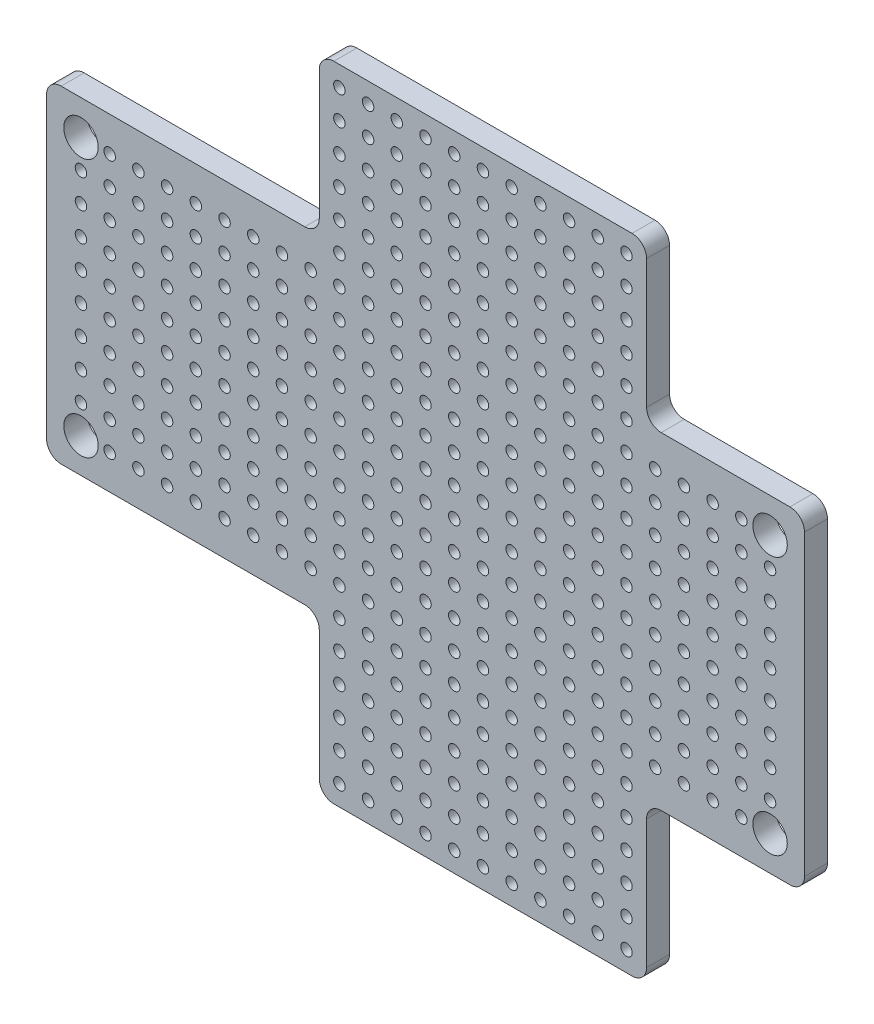
SolidWorks part; units mm, degrees
ref_plane "Front Plane" through (0, 0, 0) normal (0, 0, 1) x (1, 0, 0)
ref_plane "Top Plane" through (0, 0, 0) normal (0, 1, 0) x (1, 0, 0)
ref_plane "Right Plane" through (0, 0, 0) normal (1, 0, 0) x (0, 0, -1)
sketch "Sketch1" plane through (0, 0, 0) normal (0, 0, 1) x (1, 0, 0)
  line L0 (0, 14.25) -> (76, 14.25) construction
  line L1 (0, 0) -> (23.75, 0)
  line L2 (0, 0) -> (0, 28.5)
  line L3 (0, 28.5) -> (23.75, 28.5)
  line L4 (66, 0) -> (66, 28.5)
  line L5 (38, -42.734) -> (38, 127.234) construction
  line L6 (0, 25.5) -> (76, 25.5) construction
  line L7 (76, 3) -> (0, 3) construction
  line L8 (63, 0) -> (63, 28.5) construction
  line L9 (3, 0) -> (3, 28.5) construction
  line L12 (23.75, 28.5) -> (23.75, 42.25)
  line L13 (23.75, 42.25) -> (52.25, 42.25)
  line L14 (52.25, 42.25) -> (52.25, 28.5)
  line L15 (52.25, -13.75) -> (52.25, 0)
  line L16 (23.75, -13.75) -> (52.25, -13.75)
  line L17 (23.75, 0) -> (23.75, -13.75)
  line L18 (52.25, 28.5) -> (66, 28.5)
  line L19 (52.25, 0) -> (66, 0)
  line L20 (25.5, 25.5) -> (25.5, 28) construction
  circle A0 centre (3, 25.5) radius 1.5
  circle A1 centre (63, 25.5) radius 1.5
  circle A2 centre (3, 3) radius 1.5
  circle A3 centre (63, 3) radius 1.5
  circle A4 centre (55.5, 5.5) radius 0.5
  circle A5 centre (5.5, 3) radius 0.5
  circle A6 centre (8, 3) radius 0.5
  circle A7 centre (10.5, 3) radius 0.5
  circle A8 centre (13, 3) radius 0.5
  circle A9 centre (15.5, 3) radius 0.5
  circle A10 centre (18, 3) radius 0.5
  circle A11 centre (20.5, 3) radius 0.5
  circle A12 centre (23, 3) radius 0.5
  circle A13 centre (25.5, 3) radius 0.5
  circle A14 centre (28, 3) radius 0.5
  circle A15 centre (30.5, 3) radius 0.5
  circle A16 centre (33, 3) radius 0.5
  circle A17 centre (35.5, 3) radius 0.5
  circle A18 centre (38, 3) radius 0.5
  circle A19 centre (40.5, 3) radius 0.5
  circle A20 centre (43, 3) radius 0.5
  circle A21 centre (45.5, 3) radius 0.5
  circle A22 centre (48, 3) radius 0.5
  circle A23 centre (50.5, 3) radius 0.5
  circle A24 centre (55.5, 10.5) radius 0.5
  circle A25 centre (55.5, 8) radius 0.5
  circle A26 centre (55.5, 15.5) radius 0.5
  circle A27 centre (55.5, 18) radius 0.5
  circle A28 centre (55.5, 20.5) radius 0.5
  circle A29 centre (55.5, 23) radius 0.5
  circle A30 centre (53, 3) radius 0.5
  circle A31 centre (53, 25.5) radius 0.5
  circle A32 centre (58, 5.5) radius 0.5
  circle A33 centre (5.5, 5.5) radius 0.5
  circle A34 centre (8, 5.5) radius 0.5
  circle A35 centre (10.5, 5.5) radius 0.5
  circle A36 centre (13, 5.5) radius 0.5
  circle A37 centre (15.5, 5.5) radius 0.5
  circle A38 centre (18, 5.5) radius 0.5
  circle A39 centre (20.5, 5.5) radius 0.5
  circle A40 centre (23, 5.5) radius 0.5
  circle A41 centre (25.5, 5.5) radius 0.5
  circle A42 centre (28, 5.5) radius 0.5
  circle A43 centre (30.5, 5.5) radius 0.5
  circle A44 centre (33, 5.5) radius 0.5
  circle A45 centre (35.5, 5.5) radius 0.5
  circle A46 centre (38, 5.5) radius 0.5
  circle A47 centre (40.5, 5.5) radius 0.5
  circle A48 centre (43, 5.5) radius 0.5
  circle A49 centre (45.5, 5.5) radius 0.5
  circle A50 centre (48, 5.5) radius 0.5
  circle A51 centre (50.5, 5.5) radius 0.5
  circle A52 centre (53, 5.5) radius 0.5
  circle A53 centre (58, 10.5) radius 0.5
  circle A54 centre (58, 8) radius 0.5
  circle A55 centre (58, 15.5) radius 0.5
  circle A56 centre (58, 18) radius 0.5
  circle A57 centre (58, 20.5) radius 0.5
  circle A58 centre (58, 23) radius 0.5
  circle A59 centre (55.5, 3) radius 0.5
  circle A60 centre (55.5, 25.5) radius 0.5
  circle A61 centre (5.5, 8) radius 0.5
  circle A62 centre (8, 8) radius 0.5
  circle A63 centre (10.5, 8) radius 0.5
  circle A64 centre (13, 8) radius 0.5
  circle A65 centre (15.5, 8) radius 0.5
  circle A66 centre (18, 8) radius 0.5
  circle A67 centre (20.5, 8) radius 0.5
  circle A68 centre (23, 8) radius 0.5
  circle A69 centre (25.5, 8) radius 0.5
  circle A70 centre (28, 8) radius 0.5
  circle A71 centre (30.5, 8) radius 0.5
  circle A72 centre (33, 8) radius 0.5
  circle A73 centre (35.5, 8) radius 0.5
  circle A74 centre (38, 8) radius 0.5
  circle A75 centre (40.5, 8) radius 0.5
  circle A76 centre (43, 8) radius 0.5
  circle A77 centre (45.5, 8) radius 0.5
  circle A78 centre (48, 8) radius 0.5
  circle A79 centre (50.5, 8) radius 0.5
  circle A80 centre (53, 8) radius 0.5
  circle A81 centre (60.5, 5.5) radius 0.5
  circle A82 centre (60.5, 10.5) radius 0.5
  circle A83 centre (60.5, 8) radius 0.5
  circle A84 centre (60.5, 15.5) radius 0.5
  circle A85 centre (60.5, 18) radius 0.5
  circle A86 centre (60.5, 20.5) radius 0.5
  circle A87 centre (60.5, 23) radius 0.5
  circle A88 centre (58, 3) radius 0.5
  circle A89 centre (5.5, 10.5) radius 0.5
  circle A90 centre (8, 10.5) radius 0.5
  circle A91 centre (10.5, 10.5) radius 0.5
  circle A92 centre (13, 10.5) radius 0.5
  circle A93 centre (15.5, 10.5) radius 0.5
  circle A94 centre (18, 10.5) radius 0.5
  circle A95 centre (20.5, 10.5) radius 0.5
  circle A96 centre (23, 10.5) radius 0.5
  circle A97 centre (25.5, 10.5) radius 0.5
  circle A98 centre (28, 10.5) radius 0.5
  circle A99 centre (30.5, 10.5) radius 0.5
  circle A100 centre (33, 10.5) radius 0.5
  circle A101 centre (35.5, 10.5) radius 0.5
  circle A102 centre (38, 10.5) radius 0.5
  circle A103 centre (40.5, 10.5) radius 0.5
  circle A104 centre (43, 10.5) radius 0.5
  circle A105 centre (45.5, 10.5) radius 0.5
  circle A106 centre (48, 10.5) radius 0.5
  circle A107 centre (50.5, 10.5) radius 0.5
  circle A108 centre (53, 10.5) radius 0.5
  circle A109 centre (58, 25.5) radius 0.5
  circle A110 centre (63, 5.5) radius 0.5
  circle A111 centre (63, 10.5) radius 0.5
  circle A112 centre (63, 8) radius 0.5
  circle A113 centre (63, 15.5) radius 0.5
  circle A114 centre (63, 18) radius 0.5
  circle A115 centre (63, 20.5) radius 0.5
  circle A116 centre (63, 23) radius 0.5
  circle A117 centre (5.5, 13) radius 0.5
  circle A118 centre (8, 13) radius 0.5
  circle A119 centre (10.5, 13) radius 0.5
  circle A120 centre (13, 13) radius 0.5
  circle A121 centre (15.5, 13) radius 0.5
  circle A122 centre (18, 13) radius 0.5
  circle A123 centre (20.5, 13) radius 0.5
  circle A124 centre (23, 13) radius 0.5
  circle A125 centre (25.5, 13) radius 0.5
  circle A126 centre (28, 13) radius 0.5
  circle A127 centre (30.5, 13) radius 0.5
  circle A128 centre (33, 13) radius 0.5
  circle A129 centre (35.5, 13) radius 0.5
  circle A130 centre (38, 13) radius 0.5
  circle A131 centre (40.5, 13) radius 0.5
  circle A132 centre (43, 13) radius 0.5
  circle A133 centre (45.5, 13) radius 0.5
  circle A134 centre (48, 13) radius 0.5
  circle A135 centre (50.5, 13) radius 0.5
  circle A136 centre (53, 13) radius 0.5
  circle A137 centre (60.5, 3) radius 0.5
  circle A138 centre (60.5, 25.5) radius 0.5
  circle A139 centre (55.5, 13) radius 0.5
  circle A140 centre (58, 13) radius 0.5
  circle A141 centre (60.5, 13) radius 0.5
  circle A142 centre (63, 13) radius 0.5
  circle A145 centre (5.5, 15.5) radius 0.5
  circle A146 centre (8, 15.5) radius 0.5
  circle A147 centre (10.5, 15.5) radius 0.5
  circle A148 centre (13, 15.5) radius 0.5
  circle A149 centre (15.5, 15.5) radius 0.5
  circle A150 centre (18, 15.5) radius 0.5
  circle A151 centre (20.5, 15.5) radius 0.5
  circle A152 centre (23, 15.5) radius 0.5
  circle A153 centre (25.5, 15.5) radius 0.5
  circle A154 centre (28, 15.5) radius 0.5
  circle A155 centre (30.5, 15.5) radius 0.5
  circle A156 centre (33, 15.5) radius 0.5
  circle A157 centre (35.5, 15.5) radius 0.5
  circle A158 centre (38, 15.5) radius 0.5
  circle A159 centre (40.5, 15.5) radius 0.5
  circle A160 centre (43, 15.5) radius 0.5
  circle A161 centre (45.5, 15.5) radius 0.5
  circle A162 centre (48, 15.5) radius 0.5
  circle A163 centre (50.5, 15.5) radius 0.5
  circle A164 centre (53, 15.5) radius 0.5
  circle A173 centre (5.5, 18) radius 0.5
  circle A174 centre (8, 18) radius 0.5
  circle A175 centre (10.5, 18) radius 0.5
  circle A176 centre (13, 18) radius 0.5
  circle A177 centre (15.5, 18) radius 0.5
  circle A178 centre (18, 18) radius 0.5
  circle A179 centre (20.5, 18) radius 0.5
  circle A180 centre (23, 18) radius 0.5
  circle A181 centre (25.5, 18) radius 0.5
  circle A182 centre (28, 18) radius 0.5
  circle A183 centre (30.5, 18) radius 0.5
  circle A184 centre (33, 18) radius 0.5
  circle A185 centre (35.5, 18) radius 0.5
  circle A186 centre (38, 18) radius 0.5
  circle A187 centre (40.5, 18) radius 0.5
  circle A188 centre (43, 18) radius 0.5
  circle A189 centre (45.5, 18) radius 0.5
  circle A190 centre (48, 18) radius 0.5
  circle A191 centre (50.5, 18) radius 0.5
  circle A192 centre (53, 18) radius 0.5
  circle A201 centre (5.5, 20.5) radius 0.5
  circle A202 centre (8, 20.5) radius 0.5
  circle A203 centre (10.5, 20.5) radius 0.5
  circle A204 centre (13, 20.5) radius 0.5
  circle A205 centre (15.5, 20.5) radius 0.5
  circle A206 centre (18, 20.5) radius 0.5
  circle A207 centre (20.5, 20.5) radius 0.5
  circle A208 centre (23, 20.5) radius 0.5
  circle A209 centre (25.5, 20.5) radius 0.5
  circle A210 centre (28, 20.5) radius 0.5
  circle A211 centre (30.5, 20.5) radius 0.5
  circle A212 centre (33, 20.5) radius 0.5
  circle A213 centre (35.5, 20.5) radius 0.5
  circle A214 centre (38, 20.5) radius 0.5
  circle A215 centre (40.5, 20.5) radius 0.5
  circle A216 centre (43, 20.5) radius 0.5
  circle A217 centre (45.5, 20.5) radius 0.5
  circle A218 centre (48, 20.5) radius 0.5
  circle A219 centre (50.5, 20.5) radius 0.5
  circle A220 centre (53, 20.5) radius 0.5
  circle A229 centre (5.5, 23) radius 0.5
  circle A230 centre (8, 23) radius 0.5
  circle A231 centre (10.5, 23) radius 0.5
  circle A232 centre (13, 23) radius 0.5
  circle A233 centre (15.5, 23) radius 0.5
  circle A234 centre (18, 23) radius 0.5
  circle A235 centre (20.5, 23) radius 0.5
  circle A236 centre (23, 23) radius 0.5
  circle A237 centre (25.5, 23) radius 0.5
  circle A238 centre (28, 23) radius 0.5
  circle A239 centre (30.5, 23) radius 0.5
  circle A240 centre (33, 23) radius 0.5
  circle A241 centre (35.5, 23) radius 0.5
  circle A242 centre (38, 23) radius 0.5
  circle A243 centre (40.5, 23) radius 0.5
  circle A244 centre (43, 23) radius 0.5
  circle A245 centre (45.5, 23) radius 0.5
  circle A246 centre (48, 23) radius 0.5
  circle A247 centre (50.5, 23) radius 0.5
  circle A248 centre (53, 23) radius 0.5
  circle A257 centre (5.5, 25.5) radius 0.5
  circle A258 centre (8, 25.5) radius 0.5
  circle A259 centre (10.5, 25.5) radius 0.5
  circle A260 centre (13, 25.5) radius 0.5
  circle A261 centre (15.5, 25.5) radius 0.5
  circle A262 centre (18, 25.5) radius 0.5
  circle A263 centre (20.5, 25.5) radius 0.5
  circle A264 centre (23, 25.5) radius 0.5
  circle A265 centre (25.5, 25.5) radius 0.5
  circle A266 centre (28, 25.5) radius 0.5
  circle A267 centre (30.5, 25.5) radius 0.5
  circle A268 centre (33, 25.5) radius 0.5
  circle A269 centre (35.5, 25.5) radius 0.5
  circle A270 centre (38, 25.5) radius 0.5
  circle A271 centre (40.5, 25.5) radius 0.5
  circle A272 centre (43, 25.5) radius 0.5
  circle A273 centre (45.5, 25.5) radius 0.5
  circle A274 centre (48, 25.5) radius 0.5
  circle A275 centre (50.5, 25.5) radius 0.5
  circle A285 centre (3, 5.5) radius 0.5
  circle A286 centre (3, 8) radius 0.5
  circle A287 centre (3, 10.5) radius 0.5
  circle A288 centre (3, 13) radius 0.5
  circle A289 centre (3, 15.5) radius 0.5
  circle A290 centre (3, 18) radius 0.5
  circle A291 centre (3, 20.5) radius 0.5
  circle A292 centre (3, 23) radius 0.5
  circle A294 centre (25.5, 28) radius 0.5
  circle A295 centre (28, 28) radius 0.5
  circle A296 centre (30.5, 28) radius 0.5
  circle A297 centre (33, 28) radius 0.5
  circle A298 centre (35.5, 28) radius 0.5
  circle A299 centre (38, 28) radius 0.5
  circle A300 centre (40.5, 28) radius 0.5
  circle A301 centre (43, 28) radius 0.5
  circle A302 centre (45.5, 28) radius 0.5
  circle A303 centre (48, 28) radius 0.5
  circle A304 centre (50.5, 28) radius 0.5
  circle A305 centre (25.5, 30.5) radius 0.5
  circle A306 centre (28, 30.5) radius 0.5
  circle A307 centre (30.5, 30.5) radius 0.5
  circle A308 centre (33, 30.5) radius 0.5
  circle A309 centre (35.5, 30.5) radius 0.5
  circle A310 centre (38, 30.5) radius 0.5
  circle A311 centre (40.5, 30.5) radius 0.5
  circle A312 centre (43, 30.5) radius 0.5
  circle A313 centre (45.5, 30.5) radius 0.5
  circle A314 centre (48, 30.5) radius 0.5
  circle A315 centre (50.5, 30.5) radius 0.5
  circle A316 centre (25.5, 33) radius 0.5
  circle A317 centre (28, 33) radius 0.5
  circle A318 centre (30.5, 33) radius 0.5
  circle A319 centre (33, 33) radius 0.5
  circle A320 centre (35.5, 33) radius 0.5
  circle A321 centre (38, 33) radius 0.5
  circle A322 centre (40.5, 33) radius 0.5
  circle A323 centre (43, 33) radius 0.5
  circle A324 centre (45.5, 33) radius 0.5
  circle A325 centre (48, 33) radius 0.5
  circle A326 centre (50.5, 33) radius 0.5
  circle A327 centre (25.5, 35.5) radius 0.5
  circle A328 centre (28, 35.5) radius 0.5
  circle A329 centre (30.5, 35.5) radius 0.5
  circle A330 centre (33, 35.5) radius 0.5
  circle A331 centre (35.5, 35.5) radius 0.5
  circle A332 centre (38, 35.5) radius 0.5
  circle A333 centre (40.5, 35.5) radius 0.5
  circle A334 centre (43, 35.5) radius 0.5
  circle A335 centre (45.5, 35.5) radius 0.5
  circle A336 centre (48, 35.5) radius 0.5
  circle A337 centre (50.5, 35.5) radius 0.5
  circle A338 centre (25.5, 38) radius 0.5
  circle A339 centre (28, 38) radius 0.5
  circle A340 centre (30.5, 38) radius 0.5
  circle A341 centre (33, 38) radius 0.5
  circle A342 centre (35.5, 38) radius 0.5
  circle A343 centre (38, 38) radius 0.5
  circle A344 centre (40.5, 38) radius 0.5
  circle A345 centre (43, 38) radius 0.5
  circle A346 centre (45.5, 38) radius 0.5
  circle A347 centre (48, 38) radius 0.5
  circle A348 centre (50.5, 38) radius 0.5
  circle A349 centre (25.5, 40.5) radius 0.5
  circle A350 centre (28, 40.5) radius 0.5
  circle A351 centre (30.5, 40.5) radius 0.5
  circle A352 centre (33, 40.5) radius 0.5
  circle A353 centre (35.5, 40.5) radius 0.5
  circle A354 centre (38, 40.5) radius 0.5
  circle A355 centre (40.5, 40.5) radius 0.5
  circle A356 centre (43, 40.5) radius 0.5
  circle A357 centre (45.5, 40.5) radius 0.5
  circle A358 centre (48, 40.5) radius 0.5
  circle A359 centre (50.5, 40.5) radius 0.5
  circle A384 centre (25.5, -12) radius 0.5
  circle A385 centre (25.5, -9.5) radius 0.5
  circle A386 centre (25.5, -7) radius 0.5
  circle A387 centre (25.5, -4.5) radius 0.5
  circle A388 centre (25.5, -2) radius 0.5
  circle A389 centre (25.5, 0.5) radius 0.5
  circle A410 centre (50.5, -12) radius 0.5
  circle A411 centre (48, -12) radius 0.5
  circle A412 centre (45.5, -12) radius 0.5
  circle A413 centre (43, -12) radius 0.5
  circle A414 centre (40.5, -12) radius 0.5
  circle A415 centre (38, -12) radius 0.5
  circle A416 centre (35.5, -12) radius 0.5
  circle A417 centre (33, -12) radius 0.5
  circle A418 centre (30.5, -12) radius 0.5
  circle A419 centre (28, -12) radius 0.5
  circle A420 centre (50.5, -9.5) radius 0.5
  circle A421 centre (48, -9.5) radius 0.5
  circle A422 centre (45.5, -9.5) radius 0.5
  circle A423 centre (43, -9.5) radius 0.5
  circle A424 centre (40.5, -9.5) radius 0.5
  circle A425 centre (38, -9.5) radius 0.5
  circle A426 centre (35.5, -9.5) radius 0.5
  circle A427 centre (33, -9.5) radius 0.5
  circle A428 centre (30.5, -9.5) radius 0.5
  circle A429 centre (28, -9.5) radius 0.5
  circle A430 centre (50.5, -7) radius 0.5
  circle A431 centre (48, -7) radius 0.5
  circle A432 centre (45.5, -7) radius 0.5
  circle A433 centre (43, -7) radius 0.5
  circle A434 centre (40.5, -7) radius 0.5
  circle A435 centre (38, -7) radius 0.5
  circle A436 centre (35.5, -7) radius 0.5
  circle A437 centre (33, -7) radius 0.5
  circle A438 centre (30.5, -7) radius 0.5
  circle A439 centre (28, -7) radius 0.5
  circle A440 centre (50.5, -4.5) radius 0.5
  circle A441 centre (48, -4.5) radius 0.5
  circle A442 centre (45.5, -4.5) radius 0.5
  circle A443 centre (43, -4.5) radius 0.5
  circle A444 centre (40.5, -4.5) radius 0.5
  circle A445 centre (38, -4.5) radius 0.5
  circle A446 centre (35.5, -4.5) radius 0.5
  circle A447 centre (33, -4.5) radius 0.5
  circle A448 centre (30.5, -4.5) radius 0.5
  circle A449 centre (28, -4.5) radius 0.5
  circle A450 centre (50.5, -2) radius 0.5
  circle A451 centre (48, -2) radius 0.5
  circle A452 centre (45.5, -2) radius 0.5
  circle A453 centre (43, -2) radius 0.5
  circle A454 centre (40.5, -2) radius 0.5
  circle A455 centre (38, -2) radius 0.5
  circle A456 centre (35.5, -2) radius 0.5
  circle A457 centre (33, -2) radius 0.5
  circle A458 centre (30.5, -2) radius 0.5
  circle A459 centre (28, -2) radius 0.5
  circle A460 centre (50.5, 0.5) radius 0.5
  circle A461 centre (48, 0.5) radius 0.5
  circle A462 centre (45.5, 0.5) radius 0.5
  circle A463 centre (43, 0.5) radius 0.5
  circle A464 centre (40.5, 0.5) radius 0.5
  circle A465 centre (38, 0.5) radius 0.5
  circle A466 centre (35.5, 0.5) radius 0.5
  circle A467 centre (33, 0.5) radius 0.5
  circle A468 centre (30.5, 0.5) radius 0.5
  circle A469 centre (28, 0.5) radius 0.5
  circle A571 centre (3, 3) radius 1.5 [skipped]
  point P611 (38, 42.25)
  point P612 (38, 14.25)
  dimension "D3" = 3
  dimension "D8" = 3
  dimension "D9" = 11.25
  dimension "D10" = 38
  dimension "D11" = 35
  dimension "D1" = 28.5
  dimension "D2" = 3
  dimension "D4" = 3
  dimension "D5" = 3
  dimension "D13" = 5
  dimension "D14" = 5
  dimension "D16" = 28.5
  dimension "D17" = 13.75
  dimension "D19" = 2.5
  dimension "D12" = 13.75
  dimension "D6" = 2
  dimension "D7" = 2
  dimension "D18" = 7
extrude "Boss-Extrude1" add sketch "Sketch1" along normal blind 2
fillet "Fillet1" radius 1.27 12 edges at (0, 28.5, 1) (0, 0, 1) (52.25, 42.25, 1) (23.75, 42.25, 1) (23.75, 28.5, 1) (23.75, 0, 1) (23.75, -13.75, 1) (52.25, -13.75, 1) (52.25, 28.5, 1) (52.25, 0, 1) (66, 28.5, 1) (66, 0, 1)
ref_plane "Plane1" through (0, 14.25, 0) normal (0, -1, 0) x (1, 0, 0)
ref_plane "Plane2" through (38, 0, 0) normal (1, 0, 0) x (0, 0, -1)
